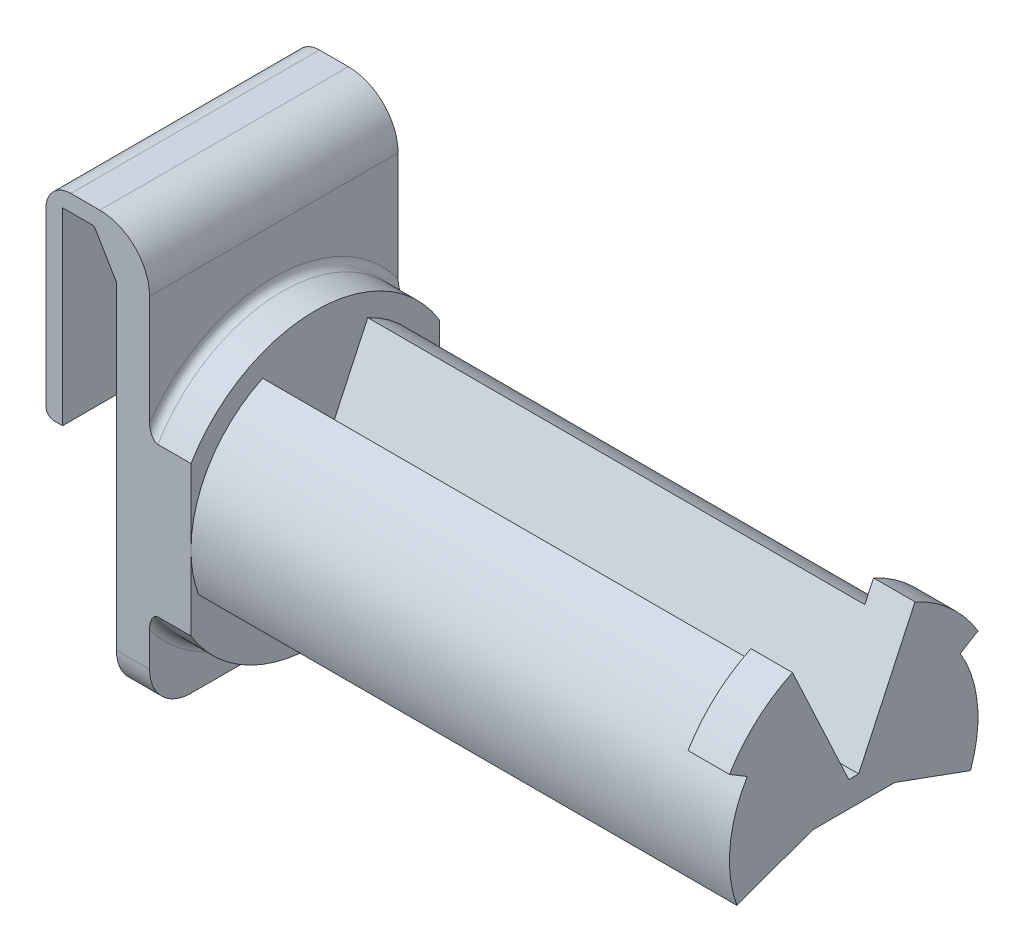
SolidWorks part; units mm, degrees
ref_plane "Front Plane" through (0, 0, 0) normal (0, 0, 1) x (1, 0, 0)
ref_plane "Top Plane" through (0, 0, 0) normal (0, 1, 0) x (1, 0, 0)
ref_plane "Right Plane" through (0, 0, 0) normal (1, 0, 0) x (0, 0, -1)
sketch "Sketch1" plane through (0, 0, 0) normal (0, 0, 1) x (1, 0, 0)
  line L0 (0, 0) -> (0, 50)
  line L1 (0, 50) -> (-12.5, 50)
  line L2 (-12.5, 50) -> (-12.5, 25.2135)
  line L3 (-12.5, 25.2135) -> (-10.5, 25.2135)
  line L4 (-10.5, 25.2135) -> (-10.5, 48)
  line L5 (-10.5, 48) -> (-6.7, 48)
  line L6 (-6.7, 48) -> (-4, 43.5)
  line L7 (-4, 43.5) -> (-4, 0)
  line L8 (-4, 0) -> (0, 0)
  dimension "D1" = 2
  dimension "D2" = 2
  dimension "D3" = 2.7
  dimension "D4" = 4.5
  dimension "D5" = 4
  dimension "D6" = 50
  dimension "D7" = 3.8
extrude "Boss-Extrude1" add sketch "Sketch1" along normal blind 30
sketch "Sketch2" plane through (0, 0, 0) normal (1, 0, 0) x (0, 0, -1)
  line L0 (-30, 50) -> (0, 50) construction
  line L1 (-30, 20) -> (-30, 29.0139)
  line L2 (-30, 0) -> (-30, 50) construction
  line L3 (0, 20) -> (0, 29.0139)
  line L4 (0, 0) -> (0, 50) construction
  line L5 (-30, 20) -> (-30, 10.9861)
  line L6 (0, 20) -> (0, 10.9861)
  circle A0 centre (-15, 20) radius 15
  arc A1 (-30, 10.9861) -> (0, 10.9861) centre (-15, 20) ccw
  arc A2 (0, 29.0139) -> (-30, 29.0139) centre (-15, 20) ccw
  dimension "D2" = 35
  dimension "D1" = 30
sketch "Sketch3" plane through (0, 0, 0) normal (1, 0, 0) x (0, 0, -1)
  line L0 (-30, 50) -> (0, 50) construction
  line L1 (-25, 50) -> (-5, 50)
  line L2 (-25, 50) -> (-25, 39.7586)
  line L3 (-25, 39.7586) -> (-25, 37.3205)
  line L4 (-5, 50) -> (-5, 39.7586)
  line L5 (-30, 0) -> (-30, 50) construction
  line L6 (0, 0) -> (0, 50) construction
  line L7 (-5, 39.7586) -> (-5, 37.3205)
  arc A0 (-5, 37.3205) -> (-25, 37.3205) centre (-15, 20) ccw
  dimension "D3" = 40
  dimension "D4" = 15
  dimension "D1" = 5
  dimension "D2" = 5
  dimension "D5" = 30
extrude "Cut-Extrude2" [suppressed] cut sketch "Sketch3" against normal blind 7
sketch "Sketch4" [suppressed] plane through (0, 50, 0) normal (0, 1, 0) x (1, 0, 0)
  line L0 (-20.3546, -30) -> (-20.3546, 0) construction
  line L1 (-20.3546, -25) -> (-15, -25)
  line L2 (-20.3546, -25) -> (-20.3546, -5)
  line L3 (-20.3546, -5) -> (-15, -5)
  line L4 (-15, -25) -> (-15, -5)
  line L5 (0, -30) -> (-20.3546, -30) construction
  line L6 (0, 0) -> (-20.3546, 0) construction
  line L7 (-7, -5) -> (-7, -25) construction
  dimension "D1" = 5
  dimension "D2" = 5
  dimension "D3" = 8
extrude "Cut-Extrude3" [suppressed] cut sketch "Sketch4" against normal blind 17
extrude "Boss-Extrude3" add sketch "Sketch2" along normal blind 5 contours A2 L1 L5 A1 L6 L3
sketch "Sketch8" plane through (5, 0, 0) normal (1, 0, 0) x (0, 0, -1)
  line L0 (-15.5939, 21.2735) -> (-14.4061, 21.2735)
  line L3 (-19.9677, 18.1919) -> (-10.0323, 18.1919)
  line L4 (-19.9677, 18.1919) -> (-29.0954, 14.8697)
  line L5 (-10.0323, 18.1919) -> (-0.9046, 14.8697)
  line L6 (-15.5939, 21.2735) -> (-21.3393, 33.5946)
  line L7 (-14.4061, 21.2735) -> (-8.6607, 33.5946)
  arc A0 (-0.9046, 14.8697) -> (-8.6607, 33.5946) centre (-15, 20) ccw
  arc A2 (-21.3393, 33.5946) -> (-29.0954, 14.8697) centre (-15, 20) ccw
sketch3d "3DSketch1" plane through (0, 0, 0) normal (0, 0, 1) x (1, 0, 0)
extrude "Boss-Extrude4" add sketch "Sketch8" along normal blind 60
sketch "Sketch9" plane through (65, 0, 0) normal (1, 0, 0) x (0, 0, -1)
  line L0 (-21.3393, 33.5946) -> (-22.3958, 35.8604)
  line L1 (-8.6607, 33.5946) -> (-7.6042, 35.8604)
  line L2 (-30, 29.0139) -> (-27.8571, 27.7262)
  line L3 (0, 29.0139) -> (-2.1429, 27.7262)
  line L4 (-21.3393, 33.5946) -> (-15.5939, 21.2735)
  line L5 (-15.5939, 21.2735) -> (-14.4061, 21.2735)
  line L6 (-14.4061, 21.2735) -> (-8.6607, 33.5946)
  line L8 (-29.0954, 14.8697) -> (-19.9677, 18.1919)
  line L9 (-19.9677, 18.1919) -> (-10.0323, 18.1919)
  line L10 (-10.0323, 18.1919) -> (-0.9046, 14.8697)
  arc A0 (-22.3958, 35.8604) -> (-30, 29.0139) centre (-15, 20) ccw
  arc A1 (-21.3393, 33.5946) -> (-29.0954, 14.8697) centre (-15, 20) ccw construction
  arc A2 (-0.9046, 14.8697) -> (-8.6607, 33.5946) centre (-15, 20) ccw construction
  arc A3 (-27.8571, 27.7262) -> (-29.0954, 14.8697) centre (-15, 20) ccw
  arc A4 (0, 29.0139) -> (-7.6042, 35.8604) centre (-15, 20) ccw
  arc A5 (-0.9046, 14.8697) -> (-2.1429, 27.7262) centre (-15, 20) ccw
extrude "Boss-Extrude5" add sketch "Sketch9" along normal blind 5
sketch "Sketch10" plane through (5, 0, 0) normal (1, 0, 0) x (0, 0, -1)
  line L0 (-24.5315, 16.5308) -> (-21.7954, 9.0133)
  line L1 (-29.0954, 14.8697) -> (-19.9677, 18.1919) construction
  dimension "D1" = 8
sketch "Sketch11" plane through (0, 22.4814, 8.1825) normal (0, -0.9397, -0.342) x (1, 0, 0)
  line L0 (5, 17.3982) -> (65, 17.3982)
  dimension "D1" = 60
ref_plane "Plane2" through (0, -5.9506, 16.349) normal (0, -0.342, 0.9397) x (1, 0, 0)
sketch "Sketch12" plane through (0, -5.9506, 16.349) normal (0, -0.342, 0.9397) x (1, 0, 0)
  line L0 (5, 15.9242) -> (65, 23.9242)
  line L1 (5, 23.9242) -> (5, 15.9242) construction
  line L2 (5, 23.9242) -> (65, 23.9242) construction
rib "Rib2" sketch "Sketch12" sketch "Sketch12" thickness 1.5 extrusion direction parallel to sketch draft on no parameters "D1"=1.5
sketch "Sketch13" plane through (5, 0, 0) normal (1, 0, 0) x (0, 0, -1)
  line L0 (-5.4685, 16.5308) -> (-8.2046, 9.0133)
  line L1 (-10.0323, 18.1919) -> (-0.9046, 14.8697) construction
  dimension "D1" = 8
sketch "Sketch14" plane through (0, 12.8395, -4.6732) normal (0, -0.9397, 0.342) x (1, 0, 0)
  line L0 (5, 10.7925) -> (65, 10.7925)
  line L1 (5, 15.6493) -> (5, 5.9358) construction
  dimension "D1" = 60
ref_plane "Plane3" through (0, 3.6913, 10.1417) normal (0, 0.342, 0.9397) x (1, 0, 0)
sketch "Sketch15" plane through (0, 3.6913, 10.1417) normal (0, 0.342, 0.9397) x (1, 0, 0)
  line L0 (5, 5.6636) -> (65, 13.6636)
rib "Rib4" sketch "Sketch15" sketch "Sketch15" thickness 1.5 extrusion direction parallel to sketch draft on no parameters "D1"=1.5
fillet "Fillet2" radius 6 1 edges at (0, 50, 15)
fillet "Fillet3" radius 3 1 edges at (-12.5, 50, 15)
fillet "Fillet4" radius 5 2 edges at (-2, 0, 0) (-2, 0, 30)
fillet "Fillet6" radius 1 4 edges at (35, 16.2743, 4.7637) (35, 16.7873, 23.8268) (35, 16.7873, 6.1732) (35, 16.2743, 25.2363)
sketch "Sketch16" plane through (5, 0, 0) normal (1, 0, 0) x (0, 0, -1)
  line L0 (-19.9677, 16.8242) -> (-10.1064, 16.8242)
  line L1 (-10.1064, 16.8242) -> (-8.4355, 16.1677)
  line L2 (-8.4355, 16.1677) -> (-12.8645, 4.8937)
  line L3 (-19.9677, 16.8242) -> (-21.5049, 16.1677)
  line L4 (-21.5049, 16.1677) -> (-16.6902, 4.8937)
  line L5 (-16.6902, 4.8937) -> (-12.8645, 4.8937)
extrude "Cut-Extrude4" cut sketch "Sketch16" against normal through all
sketch "Sketch17" plane through (-4, 0, 0) normal (-1, 0, 0) x (0, 0, 1)
  circle A0 centre (15, 20) radius 12.5
  dimension "D1" = 25
extrude "Cut-Extrude5" cut sketch "Sketch17" against normal blind 5
fillet "Fillet7" radius 1 1 edges at (-12.5, 25.2135, 15)
fillet "Fillet8" radius 1 2 edges
